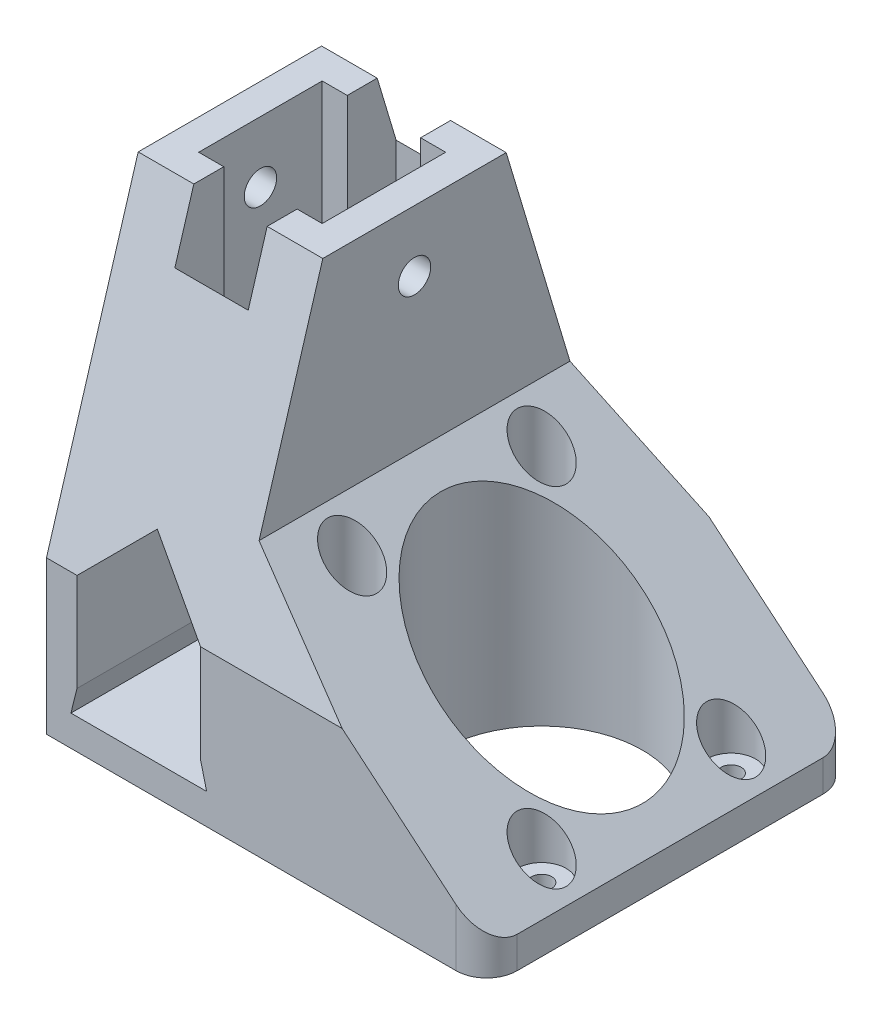
SolidWorks part; units mm, degrees
ref_plane "Front Plane" through (0, 0, 0) normal (0, 0, 1) x (1, 0, 0)
ref_plane "Top Plane" through (0, 0, 0) normal (0, 1, 0) x (1, 0, 0)
ref_plane "Right Plane" through (0, 0, 0) normal (1, 0, 0) x (0, 0, -1)
sketch "Sketch1" plane through (0, 0, 0) normal (0, 1, 0) x (1, 0, 0)
  line L1 (0, 0) -> (72, 0)
  line L2 (0, 0) -> (0, 60)
  line L3 (0, 60) -> (72, 60)
  line L4 (72, 0) -> (72, 60)
  dimension "D1" = 72
  dimension "D2" = 60
extrude "Boss-Extrude1" add sketch "Sketch1" along normal blind 5
sketch "Sketch2" plane through (0, 5, 0) normal (0, 1, 0) x (1, 0, 0)
  line L0 (0, 0) -> (72, 0) construction
  line L1 (0, 60) -> (5, 60)
  line L2 (0, 60) -> (0, 0)
  line L3 (0, 0) -> (5, 0)
  line L4 (5, 60) -> (5, 0)
  dimension "D1" = 5
extrude "Boss-Extrude2" add sketch "Sketch2" along normal blind 70
sketch "Sketch3" plane through (0, 5, 0) normal (0, 1, 0) x (1, 0, 0)
  line L0 (72, 60) -> (5, 60) construction
  line L1 (25.2, 60) -> (30.2, 60)
  line L2 (25.2, 60) -> (25.2, 0)
  line L3 (25.2, 0) -> (30.2, 0)
  line L4 (30.2, 60) -> (30.2, 0)
  line L5 (5, 0) -> (72, 0) construction
  line L6 (5, 0) -> (5, 60) construction
  dimension "D1" = 5
  dimension "D2" = 20.2
extrude "Boss-Extrude3" add sketch "Sketch3" along normal blind 70
sketch "Sketch11" plane through (0, 0, -60) normal (0, 0, -1) x (-1, 0, 0)
  line L0 (-25.2, 25) -> (-15.1, 35.1)
  line L1 (-25.2, 75) -> (-25.2, 5) construction
  line L2 (-15.1, 35.1) -> (-5, 25)
  line L3 (-5, 75) -> (-5, 5) construction
  line L4 (-5, 25) -> (-5, 75)
  line L5 (-5, 75) -> (-25.2, 75)
  line L6 (-25.2, 75) -> (-25.2, 25)
  dimension "D1" = 50
  dimension "D2" = 50
  dimension "D3" = 45
  dimension "D4" = 45
extrude "Boss-Extrude4" add sketch "Sketch11" against normal up to surface (60 mm away) up to face at (26.48, 32, 0)
chamfer "Chamfer1" distance 42 angle 40 1 edges at (30.2, 5, -30) first distance on face at (51.1, 5, -30)
chamfer "Chamfer2" distance 50 angle 16.7 2 edges at (15.1, 75, -60) (15.1, 75, 0) first distance on face at (15.1, 19.02, -60) first distance on face at (15.1, 19.02, 0)
sketch "Sketch12" plane through (0, 75, 0) normal (0, 1, 0) x (1, 0, 0)
  line L0 (0, 30) -> (30.2, 30) construction
  line L1 (5, 40.1) -> (25.2, 40.1)
  line L2 (5, 40.1) -> (5, 19.9)
  line L3 (5, 19.9) -> (25.2, 19.9)
  line L4 (25.2, 40.1) -> (25.2, 19.9)
  line L5 (5, 40.1) -> (25.2, 19.9) construction
  line L6 (5, 19.9) -> (25.2, 40.1) construction
  line L8 (30.2, 4.5729) -> (30.2, 55.4271) construction
  line L9 (0, 44.9993) -> (0, 15.0007) construction
  point P0 (15.1, 30)
  point P8 (15.2, 30)
  point P9 (15.1, 30)
  dimension "D1" = 20.2
  dimension "D2" = 20.2
  dimension "D3" = 5
extrude "Cut-Extrude8" cut sketch "Sketch12" against normal blind 67
sketch "Sketch5" plane through (0, 5, 0) normal (0, 1, 0) x (1, 0, 0)
  line L0 (72, 0) -> (72, 60) construction
  line L1 (5, 0) -> (25.2, 0) construction
  circle A0 centre (51, 30) radius 16.5
  dimension "D1" = 33
  dimension "D2" = 21
  dimension "D3" = 30
extrude "Cut-Extrude1" cut sketch "Sketch5" against normal through all both and the other way through all
sketch "Sketch6" plane through (0, 0, 0) normal (0, -1, 0) x (1, 0, 0)
  line L1 (35.5, -14.5) -> (66.5, -14.5) construction
  line L2 (35.5, -14.5) -> (35.5, -45.5) construction
  line L3 (35.5, -45.5) -> (66.5, -45.5) construction
  line L4 (66.5, -14.5) -> (66.5, -45.5) construction
  line L5 (35.5, -14.5) -> (66.5, -45.5) construction
  line L6 (35.5, -45.5) -> (66.5, -14.5) construction
  circle A0 centre (66.5, -14.5) radius 1.65
  circle A1 centre (66.5, -45.5) radius 1.65
  circle A2 centre (35.5, -45.5) radius 1.65
  circle A3 centre (35.5, -14.5) radius 1.65
  point P0 (51, -30)
  dimension "D3" = 3.3
  dimension "D1" = 31
  dimension "D2" = 31
extrude "Cut-Extrude2" cut sketch "Sketch6" against normal through all
sketch "Sketch7" plane through (0, 5, 0) normal (0, 1, 0) x (1, 0, 0)
  circle A0 centre (66.5, 45.5) radius 4
  circle A1 centre (66.5, 14.5) radius 4
  circle A2 centre (35.5, 14.5) radius 4
  circle A4 centre (35.5, 45.5) radius 4
  dimension "D1" = 8
extrude "Cut-Extrude4" cut sketch "Sketch7" along normal through all
sketch "Sketch8" plane through (30.2, 0, 0) normal (1, 0, 0) x (0, 0, -1)
  line L0 (15.0007, 75) -> (44.9993, 75) construction
  line L1 (30, 75) -> (30, 40.2422) construction
  line L2 (4.5729, 40.2422) -> (55.4271, 40.2422) construction
  circle A0 centre (30, 65) radius 2.65
  dimension "D1" = 5.3
  dimension "D2" = 10
extrude "Cut-Extrude5" cut sketch "Sketch8" against normal through all both and the other way through all
sketch "Sketch9" plane through (0, 0, 0) normal (0, -1, 0) x (1, 0, 0)
  line L1 (0, -60) -> (0, 0) construction
  line L2 (0, -30) -> (72, -30) construction
  line L3 (72, 0) -> (72, -60) construction
  circle A0 centre (15, -30) radius 2.65
  dimension "5.3" = 5.3
  dimension "D2" = 15
extrude "Cut-Extrude6" cut sketch "Sketch9" against normal through all both and the other way through all contours A0
fillet "Fillet1" radius 5 2 edges at (72, 2.5839, -60) (72, 2.5839, 0)
sketch "Sketch10" plane through (0, 0, 0) normal (-1, 0, 0) x (0, 0, 1)
  line L0 (-60, 0) -> (0, 0) construction
  line L1 (0, 25) -> (0, 0) construction
  circle A0 centre (-30, 15) radius 2.65
  dimension "D3" = 5.3
  dimension "D1" = 15
  dimension "D2" = 30
extrude "Cut-Extrude7" cut sketch "Sketch10" against normal blind 10
sketch "Sketch13" plane through (0, 0, 0) normal (0, 0, 1) x (1, 0, 0)
  line L0 (5, 5) -> (4, 5)
  line L1 (4, 5) -> (5, 9)
  line L2 (5, 9) -> (5, 5)
  line L3 (25.2, 5) -> (26.2, 5)
  line L4 (26.2, 5) -> (25.2, 9)
  line L5 (25.2, 25) -> (25.2, 5) construction
  line L6 (25.2, 9) -> (25.2, 5)
  dimension "D1" = 4
  dimension "D2" = 4
  dimension "D3" = 1
  dimension "D4" = 1
extrude "Cut-Extrude9" cut sketch "Sketch13" against normal through all both and the other way through all
sketch "Sketch14" plane through (0, 75, 0) normal (0, 1, 0) x (1, 0, 0)
  line L0 (15.1, 44.9993) -> (15.1, 15.0007) construction
  line L1 (30.2, 44.9993) -> (0, 44.9993) construction
  line L2 (0, 15.0007) -> (30.2, 15.0007) construction
  line L3 (25.2, 40.1) -> (5, 40.1) construction
  line L4 (9.1, 40.1) -> (21.1, 40.1)
  line L5 (9.1, 40.1) -> (9.1, 48.1)
  line L6 (9.1, 48.1) -> (21.1, 48.1)
  line L7 (21.1, 40.1) -> (21.1, 48.1)
  line L8 (15.1, 48.1) -> (15.1, 40.1) construction
  line L9 (5, 19.9) -> (25.2, 19.9) construction
  line L10 (9.1, 19.9) -> (21.1, 19.9)
  line L11 (9.1, 19.9) -> (9.1, 11.9)
  line L12 (9.1, 11.9) -> (21.1, 11.9)
  line L13 (21.1, 19.9) -> (21.1, 11.9)
  line L14 (15.1, 19.9) -> (15.1, 11.9) construction
  dimension "D1" = 8
  dimension "D2" = 12
  dimension "D3" = 8
  dimension "D4" = 12
extrude "Cut-Extrude10" cut sketch "Sketch14" against normal up to surface (70 mm away) up to face at (15, 5, -32.65)
